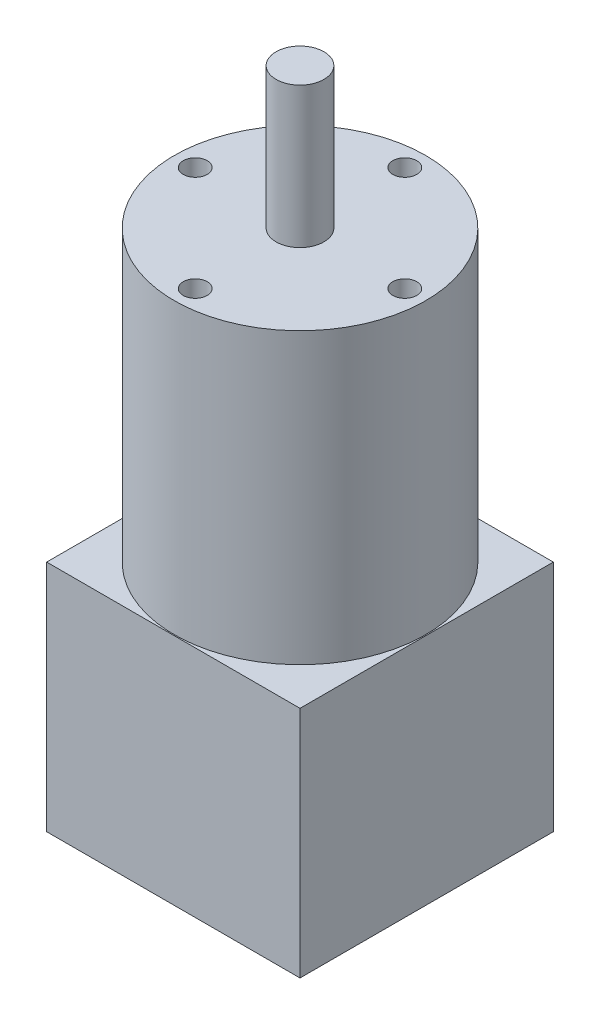
SolidWorks part; units mm, degrees
ref_plane "Front Plane" through (0, 0, 0) normal (0, 0, 1) x (1, 0, 0)
ref_plane "Top Plane" through (0, 0, 0) normal (0, 1, 0) x (1, 0, 0)
ref_plane "Right Plane" through (0, 0, 0) normal (1, 0, 0) x (0, 0, -1)
sketch "Sketch2" plane through (0, 0, 0) normal (0, 1, 0) x (1, 0, 0)
  line L1 (-21.15, -21.15) -> (21.15, -21.15)
  line L2 (-21.15, -21.15) -> (-21.15, 21.15)
  line L3 (-21.15, 21.15) -> (21.15, 21.15)
  line L4 (21.15, -21.15) -> (21.15, 21.15)
  line L5 (-21.15, -21.15) -> (21.15, 21.15) construction
  line L6 (-21.15, 21.15) -> (21.15, -21.15) construction
  point P0 (0, 0)
  dimension "D1" = 42.3
extrude "Boss-Extrude1" add sketch "Sketch2" along normal blind 39
sketch "Sketch3" plane through (0, 39, 0) normal (0, 1, 0) x (1, 0, 0)
  circle A0 centre (0, 0) radius 21
  dimension "D1" = 42
extrude "Boss-Extrude2" add sketch "Sketch3" along normal blind 48.3
sketch "Sketch4" plane through (0, 87.3, 0) normal (0, 1, 0) x (1, 0, 0)
  circle A0 centre (0, 0) radius 4
  dimension "D1" = 8
extrude "Boss-Extrude3" add sketch "Sketch4" along normal blind 23.5
sketch "Sketch5" plane through (0, 0, 0) normal (0, -1, 0) x (1, 0, 0)
  circle A0 centre (0, 0) radius 2.5
  dimension "D1" = 5
extrude "Boss-Extrude4" add sketch "Sketch5" along normal blind 9.5
sketch "Sketch6" plane through (0, 110.8, 0) normal (0, 1, 0) x (1, 0, 0)
  line L1 (-1.5, 5.2) -> (1.5, 5.2)
  line L2 (-1.5, 5.2) -> (-1.5, 2.2)
  line L3 (-1.5, 2.2) -> (1.5, 2.2)
  line L4 (1.5, 5.2) -> (1.5, 2.2)
  line L5 (-1.5, 5.2) -> (1.5, 2.2) construction
  line L6 (-1.5, 2.2) -> (1.5, 5.2) construction
  circle A0 centre (0, 0) radius 4 construction
  circle A1 centre (0, 0) radius 4 construction
  point P0 (0, 3.7)
  point P8 (0, -4)
  dimension "D1" = 3
  dimension "D2" = 3
  dimension "D3" = 9.2
extrude "Cut-Extrude1" cut sketch "Sketch6" against normal blind 14 from offset 2.6 offset against normal yes
fillet "Fillet1" radius 1.5 4 edges at (1.5, 94.2, -2.954) (-1.5, 94.2, -2.954) (1.5, 108.2, -2.954) (-1.5, 108.2, -2.954)
sketch "Sketch7" plane through (0, 87.3, 0) normal (0, 1, 0) x (1, 0, 0)
  circle A0 centre (0, 0) radius 17.5 construction
  circle A1 centre (0, 17.5) radius 2
  circle A2 centre (17.5, 0) radius 2
  circle A3 centre (0, -17.5) radius 2
  circle A4 centre (-17.5, 0) radius 2
  dimension "D1" = 35
  dimension "D2" = 4
extrude "Cut-Extrude2" cut sketch "Sketch7" against normal blind 7
